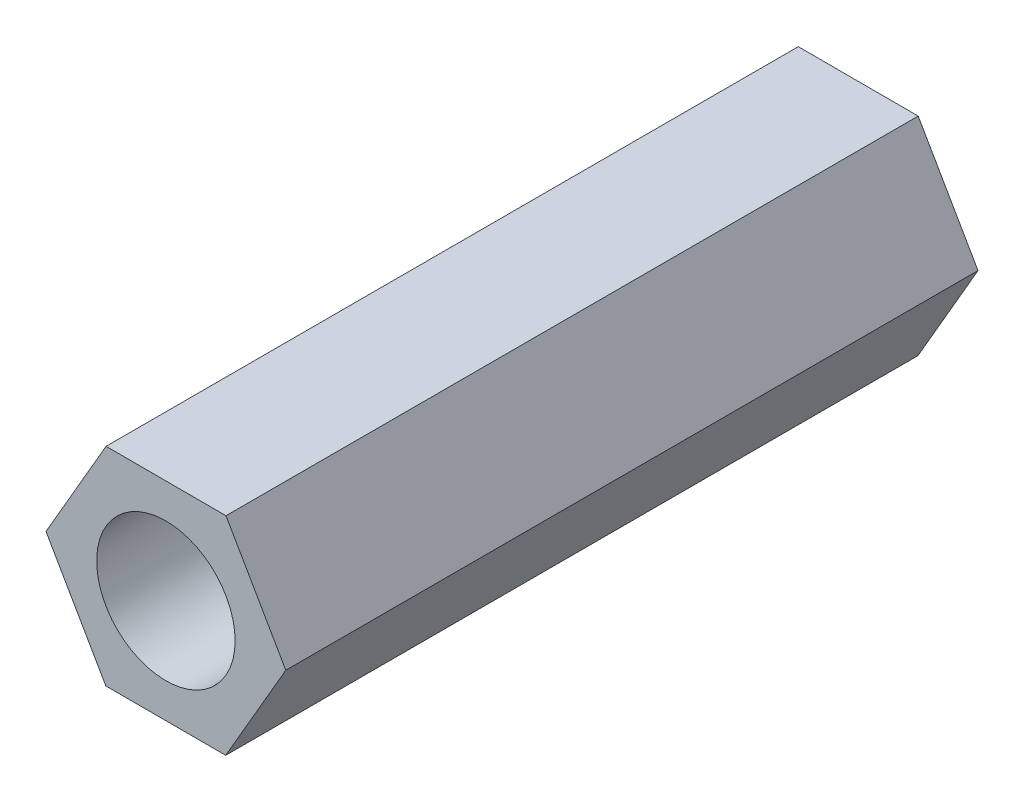
SolidWorks part; units mm, degrees
ref_plane "Front Plane" through (0, 0, 0) normal (0, 0, 1) x (1, 0, 0)
ref_plane "Top Plane" through (0, 0, 0) normal (0, 1, 0) x (1, 0, 0)
ref_plane "Right Plane" through (0, 0, 0) normal (1, 0, 0) x (0, 0, -1)
sketch "Sketch2" plane through (0, 0, 0) normal (0, 0, 1) x (1, 0, 0)
  line L1 (-1.7278, 3.0024) -> (-3.4641, 0.0049)
  line L2 (-3.4641, 0.0049) -> (-1.7363, -2.9975)
  line L3 (-1.7363, -2.9975) -> (1.7278, -3.0024)
  line L4 (1.7278, -3.0024) -> (3.4641, -0.0049)
  line L5 (3.4641, -0.0049) -> (1.7363, 2.9975)
  line L6 (1.7363, 2.9975) -> (-1.7278, 3.0024)
  circle A0 centre (0, 0) radius 3
  circle A1 centre (0, 0) radius 3 construction
  circle A2 centre (0, 0) radius 2
extrude "Boss-Extrude1" add sketch "Sketch2" along normal blind 20 contours A0 A2 | A0 L6 L1 | A0 L5 L6 | A0 L4 L5 | A0 L3 L4 | A0 L2 L3 | A0 L1 L2 region at (-1.5465, 2.6875, 0) region at (-3.1007, 0.0044, 0) region at (-1.454, 2.5267, 0) region at (1.5541, 2.6831, 0) region at (-1.5541, -2.6831, 0) region at (3.1007, -0.0044, 0) region at (1.5465, -2.6875, 0)
